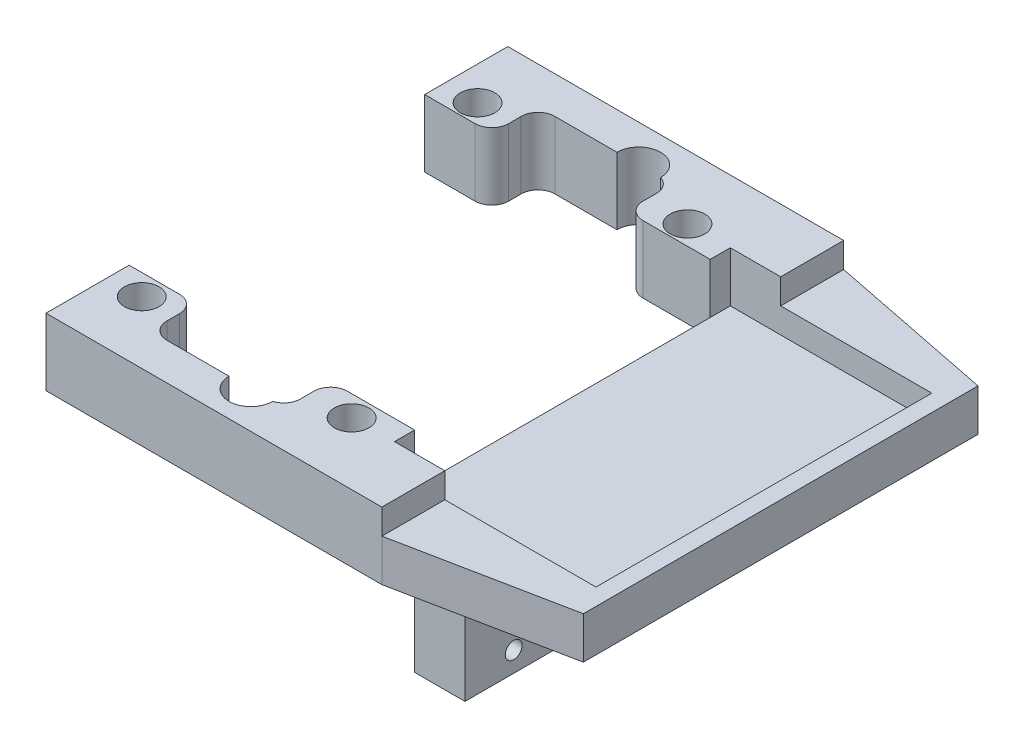
SolidWorks part; units mm, degrees
ref_plane "Front Plane" through (0, 0, 0) normal (0, 0, 1) x (1, 0, 0)
ref_plane "Top Plane" through (0, 0, 0) normal (0, 1, 0) x (1, 0, 0)
ref_plane "Right Plane" through (0, 0, 0) normal (1, 0, 0) x (0, 0, -1)
sketch "Sketch1" plane through (0, 0, 0) normal (0, 1, 0) x (1, 0, 0)
  line L0 (50.8, -0.508) -> (25.4, -5.588)
  line L1 (0, 0) -> (25.4, 0) construction
  line L2 (0, 0) -> (0, 58.674) construction
  line L3 (0, 58.674) -> (25.4, 58.674) construction
  line L4 (25.4, 0) -> (25.4, 58.674) construction
  line L5 (-25.4, 64.262) -> (25.4, 64.262)
  line L6 (-25.4, 64.262) -> (-25.4, -5.588)
  line L7 (-25.4, -5.588) -> (25.4, -5.588)
  line L8 (25.4, 64.262) -> (25.4, -5.588)
  line L9 (25.4, 59.182) -> (50.8, 59.182)
  line L10 (25.4, 59.182) -> (25.4, -0.508)
  line L11 (25.4, -0.508) -> (50.8, -0.508)
  line L12 (50.8, 59.182) -> (50.8, -0.508)
  line L13 (50.8, 59.182) -> (25.4, 64.262)
  circle A0 centre (0, 0) radius 3.302
  circle A1 centre (0, 58.674) radius 3.302
  circle A2 centre (11.43, 54.61) radius 2.6155
  circle A3 centre (-20.32, 54.61) radius 2.6155
  circle A4 centre (11.43, 3.81) radius 2.6155
  circle A5 centre (-20.32, 54.61) radius 2.6155
  circle A6 centre (-20.32, 3.81) radius 2.6155
  circle A7 centre (11.43, 3.81) radius 2.6155
  dimension "D1" = 6.604
  dimension "D3" = 6.604
  dimension "D11" = 11.43
  dimension "D12" = 4.064
  dimension "D2" = 58.674
  dimension "D4" = 25.4
  dimension "D5" = 69.85
  dimension "D6" = 5.588
  dimension "D7" = 50.8
  dimension "D8" = 25.4
  dimension "D9" = 59.69
  dimension "D10" = 5.08
  dimension "D13" = 2
  dimension "D14" = 2
  dimension "D15" = 2
  dimension "D16" = 2
extrude "Boss-Extrude1" add sketch "Sketch1" along normal blind 6.35 contours L8 L5 L6 L7 A1 A0 | L9 L13 L8 | L12 L9 L8 L11 | L11 L8 L0 region at (33.8667, 0, 2.2013) region at (38.1, 0, -29.337) region at (0.1126, 0, -29.3402) region at (33.8667, 0, -60.8753)
sketch "Sketch2" plane through (0, 6.35, 0) normal (0, 1, 0) x (1, 0, 0)
  line L0 (50.8, 59.182) -> (50.8, -0.508) construction
  line L5 (25.4, 64.262) -> (25.4, -5.588) construction
  line L6 (50.8, 59.182) -> (-25.4, 59.182) construction
  line L7 (-25.4, 64.262) -> (-25.4, -5.588) construction
  line L8 (50.8, -0.508) -> (-25.4, -0.508) construction
  line L9 (17.78, 54.737) -> (48.26, 54.737)
  line L14 (17.78, 54.737) -> (17.78, 3.937)
  line L15 (17.78, 3.937) -> (48.26, 3.937)
  line L16 (48.26, 54.737) -> (48.26, 3.937)
  dimension "D1" = 30.48
  dimension "D2" = 50.8
  dimension "D3" = 4.445
  dimension "D4" = 2.54
  dimension "D5" = 4.445
extrude "Cut-Extrude1" cut sketch "Sketch2" against normal blind 3.81
sketch "Sketch3" plane through (0, 6.35, 0) normal (0, 1, 0) x (1, 0, 0)
  line L0 (-25.4, 64.262) -> (-25.4, -5.588) construction
  line L1 (-25.4, 51.689) -> (17.78, 51.689)
  line L2 (-25.4, 51.689) -> (-25.4, 6.985)
  line L3 (-25.4, 6.985) -> (17.78, 6.985)
  line L4 (17.78, 51.689) -> (17.78, 6.985)
  line L5 (25.4, 64.262) -> (25.4, -5.588) construction
  line L7 (-25.4, 64.262) -> (25.4, 64.262) construction
  line L8 (-15.24, 51.689) -> (5.08, 51.689)
  line L9 (-15.24, 51.689) -> (-15.24, 58.674)
  line L10 (-15.24, 58.674) -> (5.08, 58.674)
  line L11 (5.08, 51.689) -> (5.08, 58.674)
  line L12 (-15.24, 6.985) -> (5.08, 6.985)
  line L13 (-15.24, 6.985) -> (-15.24, 0)
  line L14 (-15.24, 0) -> (5.08, 0)
  line L15 (5.08, 6.985) -> (5.08, 0)
  line M5 (17.78, 3.937) -> (17.78, 54.737)
  line M13 (-25.4, 64.262) -> (-25.4, -5.588)
  circle M15 centre (0, 58.674) radius 3.302
  circle M16 centre (0, 0) radius 3.302
  dimension "D1" = 44.704
  dimension "D2" = 12.573
  dimension "D3" = 10.16
  dimension "D4" = 20.32
  dimension "D5" = 58.674
  dimension "D6" = 6.985
  dimension "D7" = 6.985
  dimension "D8" = 7.62
extrude "Cut-Extrude2" cut sketch "Sketch3" against normal through all contours L1 L11 L10 L9 M15 | L3 L1 M13 M5 | L15 L3 L13 L14 M16 region at (-3.81, 6.35, -29.337) region at (-5.7771, 6.35, -54.8946) region at (-5.7771, 6.35, -3.7794)
sketch "Sketch13" plane through (0, 6.35, 0) normal (0, 1, 0) x (1, 0, 0)
  line L1 (-25.4, 51.689) -> (25.4, 51.689)
  line L2 (-25.4, 51.689) -> (-25.4, 64.262)
  line L3 (-25.4, 64.262) -> (25.4, 64.262)
  line L4 (25.4, 51.689) -> (25.4, 64.262)
  line L5 (-25.4, 6.985) -> (25.4, 6.985)
  line L6 (-25.4, 6.985) -> (-25.4, -5.588)
  line L7 (-25.4, -5.588) -> (25.4, -5.588)
  line L8 (25.4, 6.985) -> (25.4, -5.588)
  line L9 (17.78, 54.737) -> (25.4, 54.737)
  line L10 (17.78, 54.737) -> (17.78, 51.689)
  line L11 (17.78, 51.689) -> (25.4, 51.689)
  line L12 (25.4, 54.737) -> (25.4, 51.689)
  line L13 (17.78, 3.937) -> (25.4, 3.937)
  line L14 (17.78, 3.937) -> (17.78, 6.985)
  line L15 (17.78, 6.985) -> (25.4, 6.985)
  line L16 (25.4, 3.937) -> (25.4, 6.985)
  circle M1 centre (-20.32, 3.81) radius 2.6155
  circle M2 centre (11.43, 3.81) radius 2.6155
  circle M3 centre (-20.32, 54.61) radius 2.6155
  circle M4 centre (11.43, 54.61) radius 2.6155
  arc M5 (-3.302, 58.674) -> (3.302, 58.674) centre (0, 58.674) cw
  line M6 (3.302, 58.674) -> (5.08, 58.674)
  line M7 (5.08, 58.674) -> (5.08, 51.689)
  line M8 (5.08, 51.689) -> (17.78, 51.689)
  line M9 (17.78, 51.689) -> (17.78, 54.737)
  line M10 (17.78, 54.737) -> (48.26, 54.737)
  line M12 (48.26, 3.937) -> (17.78, 3.937)
  line M13 (17.78, 3.937) -> (17.78, 6.985)
  line M14 (17.78, 6.985) -> (5.08, 6.985)
  line M15 (5.08, 6.985) -> (5.08, 0)
  line M16 (5.08, 0) -> (3.302, 0)
  arc M17 (3.302, 0) -> (-3.302, 0) centre (0, 0) cw
  line M18 (-3.302, 0) -> (-15.24, 0)
  line M19 (-15.24, 0) -> (-15.24, 6.985)
  line M20 (-15.24, 6.985) -> (-25.4, 6.985)
  line M21 (-25.4, 6.985) -> (-25.4, -5.588)
  line M22 (-25.4, -5.588) -> (25.4, -5.588)
  line M26 (25.4, 64.262) -> (-25.4, 64.262)
  line M27 (-25.4, 64.262) -> (-25.4, 51.689)
  line M28 (-25.4, 51.689) -> (-15.24, 51.689)
  line M29 (-15.24, 51.689) -> (-15.24, 58.674)
  line M30 (-15.24, 58.674) -> (-3.302, 58.674)
extrude "Boss-Extrude7" add sketch "Sketch13" along normal blind 3.81 contours L4 M10 M26 M27 M28 M29 M30 M5 M6 M7 M8 M9 M3 M4 | L8 M12 M13 M14 M15 M16 M17 M18 M19 M20 M21 M22 M2 M1 region at (-24.8767, 6.35, -57.9755) region at (-20.32, 6.35, -6.4617)
sketch "Sketch15" plane through (0, 0, 0) normal (0, -1, 0) x (1, 0, 0)
  line L0 (25.4, 5.588) -> (25.4, -64.262) construction
  line L1 (5.08, -6.985) -> (17.78, -6.985) construction
  line L2 (17.78, -6.985) -> (25.4, -6.985)
  line L3 (17.78, -6.985) -> (17.78, -51.689)
  line L4 (17.78, -51.689) -> (25.4, -51.689)
  line L5 (25.4, -6.985) -> (25.4, -51.689)
  line L6 (5.08, -51.689) -> (17.78, -51.689) construction
  dimension "D1" = 44.704
extrude "Boss-Extrude8" add sketch "Sketch15" along normal blind 21.59
sketch "Sketch16" plane through (17.78, 0, 0) normal (-1, 0, 0) x (0, 0, 1)
  line L0 (-6.985, -21.59) -> (-51.689, -21.59) construction
  line L1 (-51.689, -21.59) -> (-51.689, 0) construction
  circle A0 centre (-44.323, -18.542) radius 1.27
  circle A1 centre (-34.671, -18.542) radius 1.27
  circle A2 centre (-24.003, -18.542) radius 1.27
  circle A3 centre (-14.351, -18.542) radius 1.27
  dimension "D1" = 2.54
  dimension "D2" = 3.048
  dimension "D7" = 7.366
  dimension "D3" = 2
  dimension "D4" = 2
  dimension "D5" = 2
extrude "Cut-Extrude3" cut sketch "Sketch16" against normal through all
fillet "Fillet1" radius 2.54 8 edges at (-15.24, 5.08, -6.985) (-15.24, 5.08, 0) (5.08, 5.08, 0) (5.08, 5.08, -6.985) (5.08, 5.08, -51.689) (-15.24, 5.08, -51.689) (-15.24, 5.08, -58.674) (5.08, 5.08, -58.674)
chamfer "Chamfer2" distance 2.54 angle 45 3 edges at (21.59, 0, -51.689) (21.59, 0, -6.985) (25.4, 0, -29.337)
